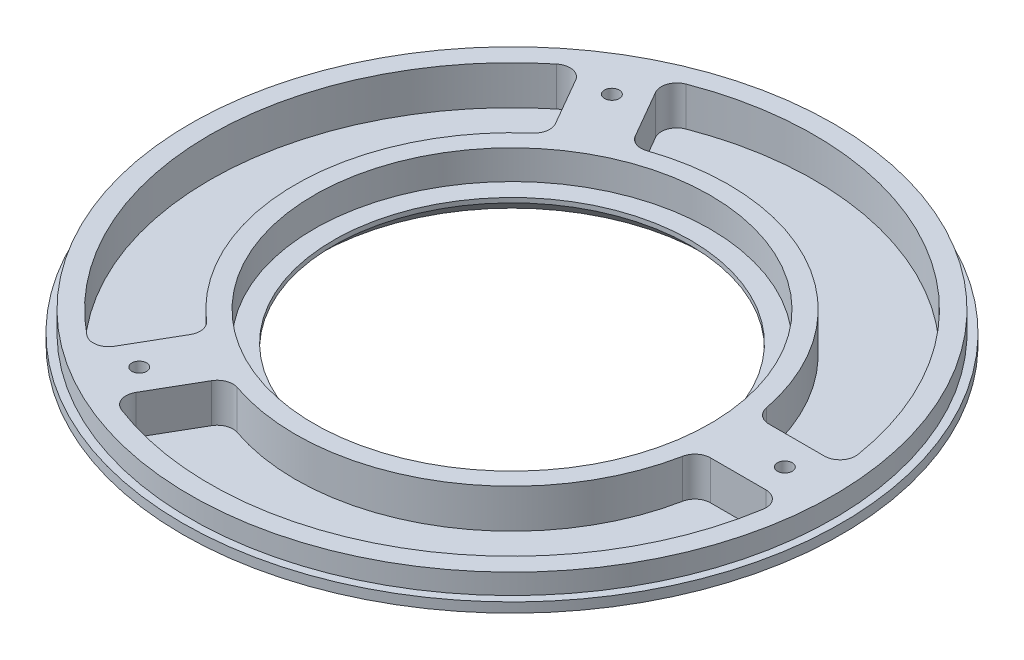
SolidWorks part; units mm, degrees
material "6061-T6 (SS)"
ref_plane "Front Plane" through (0, 0, 0) normal (0, 0, 1) x (1, 0, 0)
ref_plane "Top Plane" through (0, 0, 0) normal (0, 1, 0) x (1, 0, 0)
ref_plane "Right Plane" through (0, 0, 0) normal (1, 0, 0) x (0, 0, -1)
sketch "Sketch2" plane through (0, 0, 0) normal (1, 0, 0) x (0, 0, -1)
  line L0 (-45.8, 0) -> (-82.55, 0)
  line L1 (-82.55, 0) -> (-82.55, 12.7)
  line L2 (-82.55, 12.7) -> (-50.8, 12.7)
  line L3 (-45.8, 0) -> (-45.8, 5.2)
  line L4 (-45.8, 5.2) -> (-50.8, 5.2)
  line L5 (-50.8, 5.2) -> (-50.8, 12.7)
  line L6 (-80.2166, 12.7) -> (-80.2166, 0) construction
  dimension "D1" = 82.55
  dimension "D2" = 12.7
  dimension "D3" = 50.8
  dimension "D4" = 5
  dimension "D5" = 7.5
ref_axis "Axis1" through (0, -0.5, 0) along (0, 1, 0)
revolve "Revolve1" add sketch "Sketch2" angle 360 about axis through (0, -0.5, 0) along (0, 1, 0)
hole_wizard "#90 (0.0087) Diameter Hole1" positions "Sketch6" profile "Sketch7" hole size "#90" standard "ANSI Inch" end condition through all
sketch "Sketch6" plane through (0, 12.7, 0) normal (0, 1, 0) x (1, 0, 0)
  line L0 (0, 0) -> (-69.8201, 120.932) construction
  line L2 (0, 0) -> (0, 109.0908) construction
  point P0 (-35, 60.6218)
  dimension "D1" = 30
  dimension "D2" = 70
sketch "Sketch7" plane through (-35, 12.7, -60.6218) normal (1, 0, 0) x (0, 0, 1)
  line L0 (0, 0) -> (0, 12.7)
  line L1 (0, 12.7) -> (0.1105, 12.7)
  line L2 (0.1105, 12.7) -> (0.1105, 0)
  line L5 (0.1105, 0) -> (0, 0)
  line L11 (0, -6.35) -> (0, 107.95) construction
  dimension "Thru Hole Dia." = 0.221
  dimension "Thru Hole Depth" = 12.7
pattern_circular "CirPattern3" count 3 over 360 about axis through (0, -0.5, 0) along (0, 1, 0) of "#90 (0.0087) Diameter Hole1"
sketch "Sketch8" plane through (0, 12.7, 0) normal (0, 1, 0) x (1, 0, 0)
  line L4 (0, 0) -> (46.9997, 81.4059) construction
  line L5 (-21.0255, 51.4172) -> (-32.098, 70.5955)
  line L6 (55.0414, 7.5) -> (77.1865, 7.5)
  line L7 (0, 0) -> (-35, 60.6218) construction
  arc A0 (-21.0255, 51.4172) -> (55.0414, 7.5) centre (0, 0) cw
  arc A1 (-32.098, 70.5955) -> (77.1865, 7.5) centre (0, 0) cw
  circle A2 centre (0, 0) radius 82.55 construction
  dimension "D1" = 27
  dimension "D2" = 5
  dimension "D3" = 7.5
  dimension "D4" = 60
extrude "Cut-Extrude1" cut sketch "Sketch8" against normal blind 10
fillet "Fillet1" radius 4 4 edges at (-21.0255, 7.7, -51.4172) (55.0414, 7.7, -7.5) (77.1865, 7.7, -7.5) (-32.098, 7.7, -70.5955)
pattern_circular "CirPattern4" count 3 over 360 about axis through (0, -0.5, 0) along (0, 1, 0) of "Cut-Extrude1", "Fillet1"
chamfer "Chamfer1" distance 4 angle 45 1 edges at (0, 0, -45.8)
sketch "Sketch10" plane through (0, 0, 0) normal (0, -1, 0) x (1, 0, 0)
  circle A0 centre (0, 0) radius 82.55
  circle A1 centre (0, 0) radius 84.55
  circle A2 centre (0, 0) radius 82.55 construction
  dimension "D1" = 2
extrude "Boss-Extrude1" add sketch "Sketch10" against normal blind 7.5
chamfer "Chamfer3" distance 5 angle 60 1 edges at (0, 0, -84.55) first distance on face at (0, 7.5, -84.55)
fillet "Fillet4" radius 5 1 edges at (0, 0, 75.8897)
hole_wizard "CBORE for #6 Binding Head Machine Screw1" positions "Sketch13" profile "Sketch14" counterbore size "#6" standard "ANSI Inch" end condition through all
sketch "Sketch13" plane through (0, 0, 0) normal (0, -1, 0) x (-1, 0, 0)
  point P4 (35, 60.6218)
  point P8 (0, 0)
sketch "Sketch14" plane through (-35, 0, -60.6218) normal (1, 0, 0) x (0, 0, -1)
  line L0 (0, 0) -> (0, 12.7)
  line L1 (0, 12.7) -> (1.8986, 12.7)
  line L3 (1.8986, 12.7) -> (1.8987, 2.2098)
  line L4 (1.8987, 2.2098) -> (3.9688, 2.2098)
  line L5 (3.9688, 2.2098) -> (3.9688, 0)
  line L7 (3.9688, 0) -> (0, 0)
  line L11 (0, -6.35) -> (0, 107.95) construction
  dimension "Thru Hole Dia." = 3.7973
  dimension "Thru Hole Depth" = 12.7
  dimension "C'Bore Dia." = 7.9375
  dimension "C'Bore Depth" = 2.2098
pattern_circular "CirPattern5" count 3 over 360 about axis through (0, -0.5, 0) along (0, 1, 0) of "CBORE for #6 Binding Head Machine Screw1"
equation "\"TubeDiameter\" = 6.500in"
